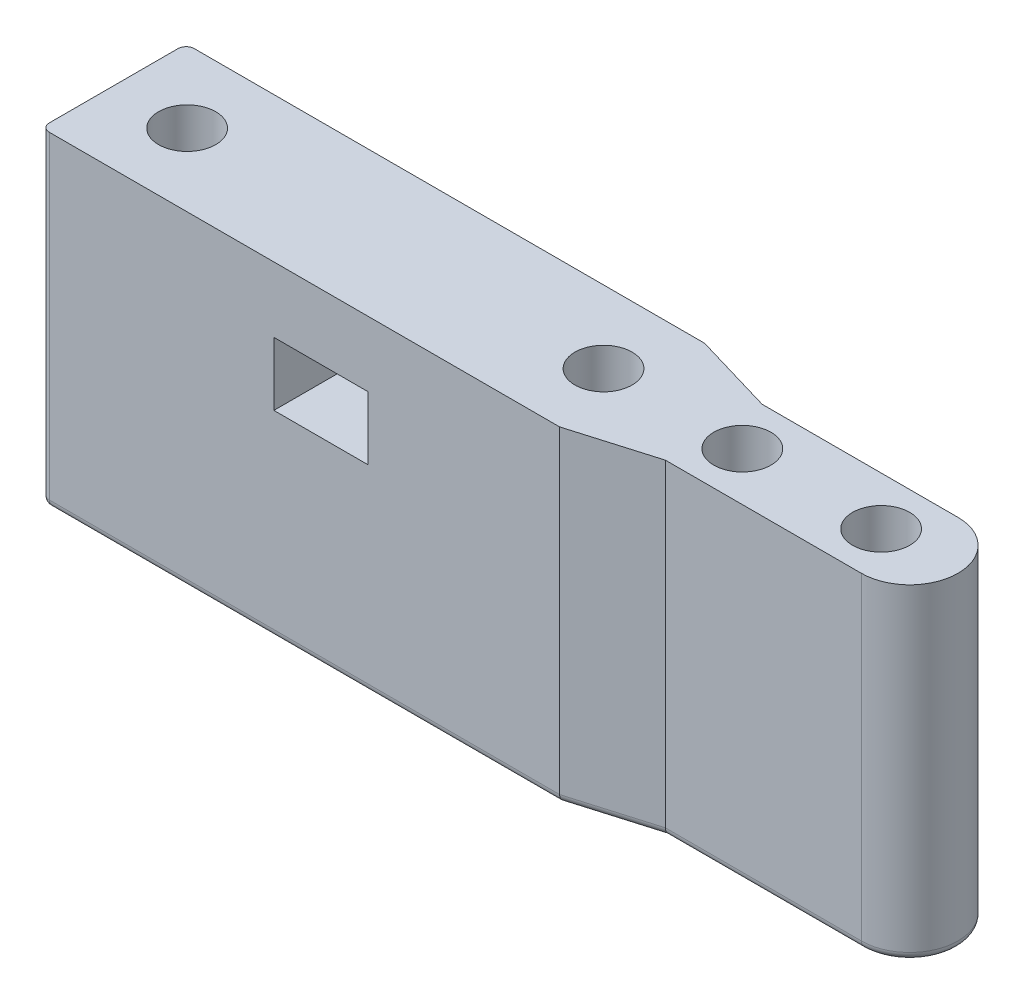
SolidWorks part; units mm, degrees
ref_plane "Front Plane" through (0, 0, 0) normal (0, 0, 1) x (1, 0, 0)
ref_plane "Top Plane" through (0, 0, 0) normal (0, 1, 0) x (1, 0, 0)
ref_plane "Right Plane" through (0, 0, 0) normal (1, 0, 0) x (0, 0, -1)
sketch "Sketch1" plane through (0, 0, 0) normal (0, 0, 1) x (1, 0, 0)
  line L1 (-58.9649, 16.1548) -> (-47.4649, 16.1548)
  line L2 (-58.9649, 16.1548) -> (-58.9649, 8.4048)
  line L3 (-58.9649, 8.4048) -> (-47.4649, 8.4048)
  line L4 (-47.4649, 16.1548) -> (-47.4649, 8.4048)
  line L5 (-87.4649, 24.1548) -> (16.5351, 24.1548)
  line L6 (-87.4649, 24.1548) -> (-87.4649, -15.8452)
  line L7 (-87.4649, -15.8452) -> (16.5351, -15.8452)
  line L8 (16.5351, 24.1548) -> (16.5351, -15.8452)
  dimension "D1" = 11.5
  dimension "D2" = 7.75
  dimension "D3" = 104
  dimension "D4" = 32
  dimension "D5" = 8
  dimension "D6" = 28.5
  dimension "D7" = 40
extrude "modular_main_body" add sketch "Sketch1" along normal blind 17.75
sketch "Sketch2" plane through (0, -15.8452, 0) normal (0, -1, 0) x (1, 0, 0)
  line L0 (16.5351, 17.75) -> (16.5351, 0) construction
  line L1 (-87.4649, 17.75) -> (16.5351, 17.75) construction
  line L2 (-87.4649, 17.75) -> (-87.4649, 0) construction
  line L3 (-23.9649, 17.75) -> (-13.9649, 14.8)
  line L8 (-87.4649, 0) -> (16.5351, 0) construction
  line L9 (10.0351, 17.75) -> (10.0351, 0) construction
  line L11 (-13.9649, 14.8) -> (10.0351, 14.8)
  line L12 (10.0351, 2.95) -> (-13.9649, 2.95)
  line L14 (-23.9649, 0) -> (-13.9649, 2.95)
  line L15 (-23.9649, 17.75) -> (16.5351, 17.75)
  line L16 (16.5351, 17.75) -> (16.5351, 0)
  line L17 (16.5351, 0) -> (-23.9649, 0)
  arc A0 (10.0351, 2.95) -> (10.0351, 14.8) centre (10.0351, 8.875) ccw
  dimension "D1" = 11.85
  dimension "D2" = 6.5
  dimension "D3" = 0
  dimension "D4" = 24
  dimension "D5" = 24
  dimension "D6" = 0
  dimension "D7" = 63.5
  dimension "D8" = 0
  dimension "D9" = 63.5
extrude "front_cut_out" cut sketch "Sketch2" against normal through all
sketch "Sketch5" plane through (0, 24.1548, 0) normal (0, 1, 0) x (1, 0, 0)
  line L1 (-87.4649, -17.75) -> (-87.4649, 0) construction
  line L2 (-78.4649, 0) -> (-78.4649, -17.75) construction
  line L3 (-23.9649, 0) -> (-87.4649, 0) construction
  line L4 (-23.9649, -17.75) -> (-87.4649, -17.75) construction
  circle A0 centre (-78.4649, -8.875) radius 3.5
  circle A3 centre (-27.4649, -8.875) radius 3.5
  circle A4 centre (-10.4649, -8.875) radius 3.5
  circle A5 centre (6.5351, -8.875) radius 3.5
  circle A6 centre (-61.4649, -8.875) radius 3.5 [skipped]
  circle A7 centre (-44.4649, -8.875) radius 3.5 [skipped]
  dimension "D1" = 7
  dimension "D3" = 9
  dimension "D5" = 51
  dimension "D4" = 6
extrude "modular_interface_deep_cut_out" cut sketch "Sketch5" against normal blind 10
fillet "Fillet1" radius 1 8 edges at (-87.4649, -15.8452, 8.875) (-55.7149, -15.8452, 17.75) (-18.9649, -15.8452, 16.275) (-1.9649, -15.8452, 14.8) (15.9601, -15.8452, 8.875) (-1.9649, -15.8452, 2.95) (-18.9649, -15.8452, 1.475) (-55.7149, -15.8452, 0)
fillet "Fillet3" radius 1 4 edges at (-87.172, -15.5523, 17.4571) (-87.172, -15.5523, 0.2929) (-87.4649, 4.6548, 17.75) (-87.4649, 4.6548, 0)
